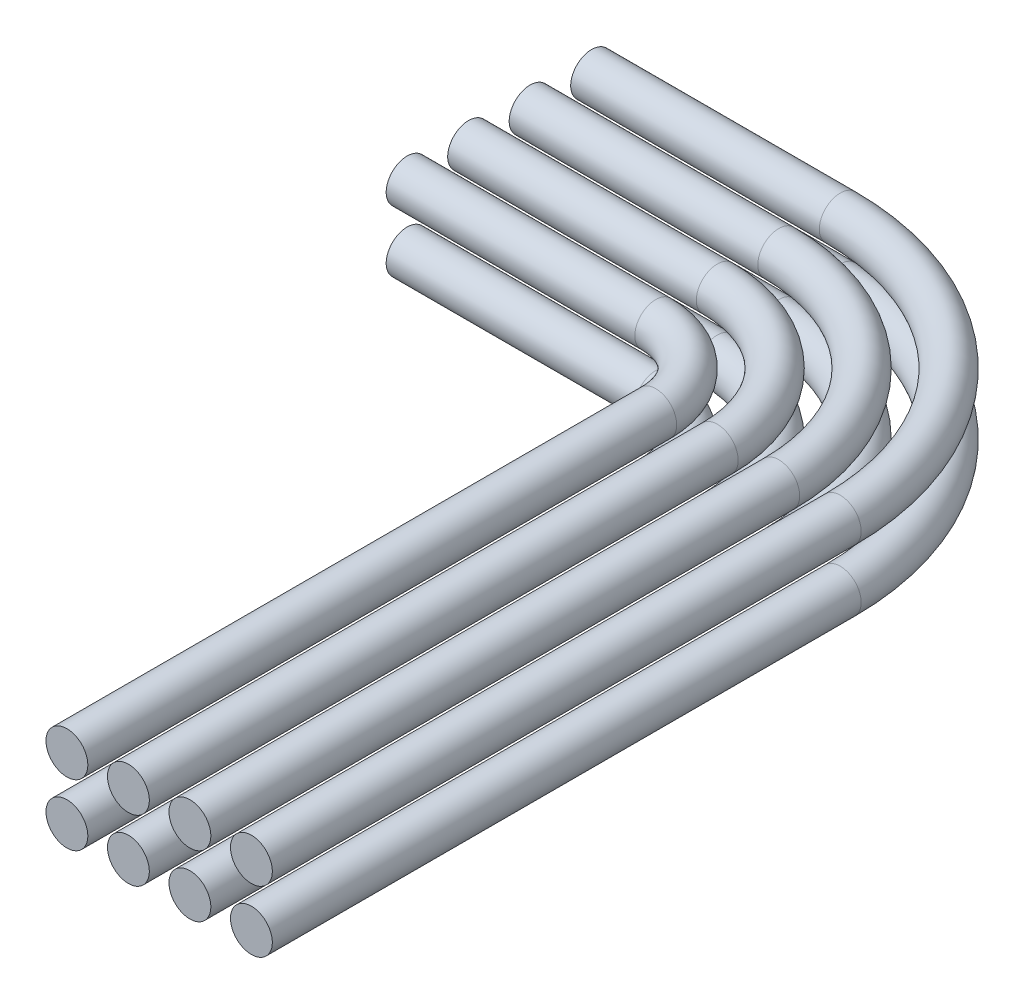
SolidWorks part; units mm, degrees
ref_plane "Front Plane" through (0, 0, 0) normal (0, 0, 1) x (1, 0, 0)
ref_plane "Top Plane" through (0, 0, 0) normal (0, 1, 0) x (1, 0, 0)
ref_plane "Right Plane" through (0, 0, 0) normal (1, 0, 0) x (0, 0, -1)
sketch "Sketch1" plane through (0, 0, 0) normal (0, 1, 0) x (1, 0, 0)
  line L0 (0, 0) -> (19, 0)
  line L1 (39, -20) -> (39, -65)
  line L2 (0, -4.7) -> (19, -4.7)
  line L3 (34.3, -20) -> (34.3, -65)
  line L4 (0, -4.7) -> (0, 0) construction
  line L5 (39, -65) -> (34.3, -65) construction
  line L6 (0, -4.7) -> (0, -9.4) construction
  line L7 (0, -9.4) -> (0, -14.1) construction
  line L8 (34.3, -65) -> (29.6, -65) construction
  line L9 (29.6, -65) -> (24.9, -65) construction
  line L10 (0, -9.4) -> (19, -9.4)
  line L11 (29.6, -20) -> (29.6, -65)
  line L12 (24.9, -65) -> (24.9, -20)
  line L13 (19, -14.1) -> (0, -14.1)
  line L14 (19, 0) -> (19, -14.1) construction
  line L15 (24.9, -20) -> (39, -20) construction
  arc A0 (19, -4.7) -> (34.3, -20) centre (19, -20) cw
  arc A1 (19, 0) -> (39, -20) centre (19, -20) cw
  arc A2 (19, -9.4) -> (29.6, -20) centre (19, -20) cw
  arc A3 (24.9, -20) -> (19, -14.1) centre (19, -20) ccw
  point P11 (39, 0)
  dimension "D5" = 20
  dimension "D1" = 4.7
  dimension "D2" = 19
  dimension "D3" = 65
ref_plane "Plane1" through (0, 0, 0) normal (1, 0, 0) x (0, 0, -1)
sketch "Sketch2" plane through (0, 0, 0) normal (1, 0, 0) x (0, 0, -1)
  circle A0 centre (0, 0) radius 1.6
  circle A1 centre (-4.7, 0) radius 1.6
  circle A2 centre (-9.4, 0) radius 1.6
  circle A3 centre (-14.1, 0) radius 1.6
  dimension "D1" = 3.2
sweep "Sweep1" add profiles "Sketch2" path "Sketch1"
sketch "Sketch3" plane through (0, 0, 0) normal (1, 0, 0) x (0, 0, -1)
  line L0 (0, 0) -> (0, 4.7) construction
  dimension "D1" = 4.7
pattern_linear "LPattern1" count 2 spacing 4.7 along (0, 1, 0) of "Sweep1"
